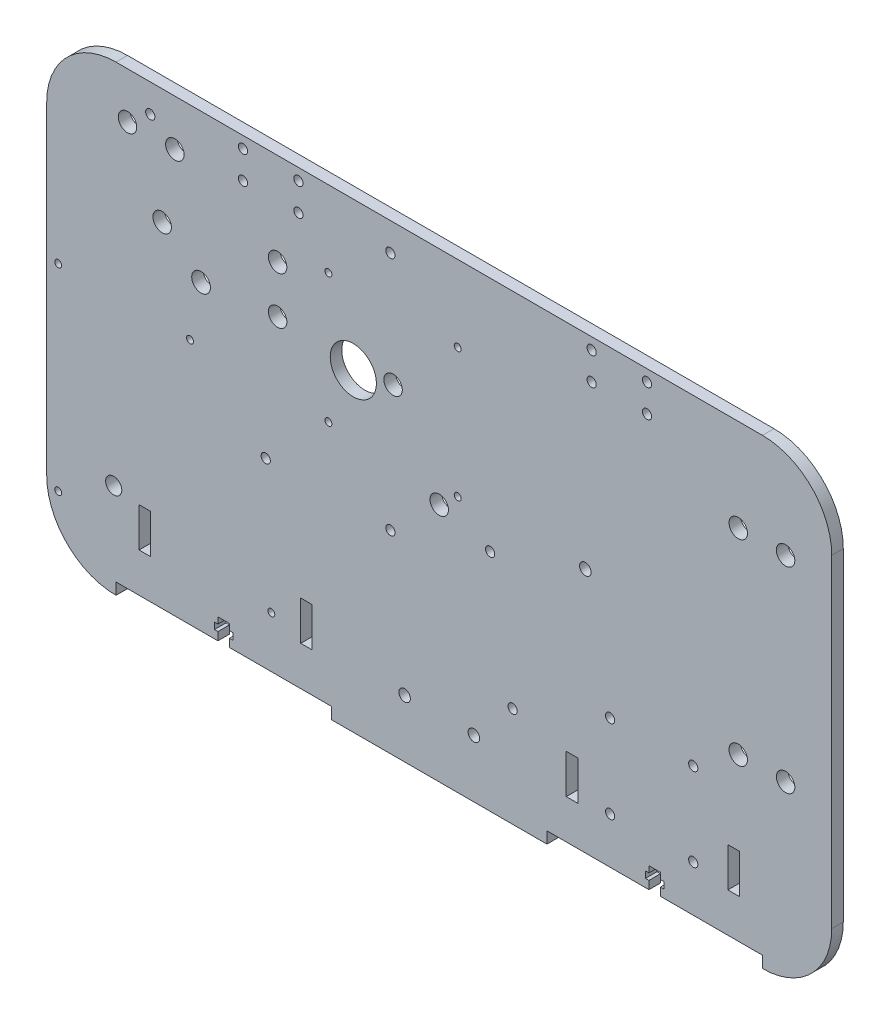
SolidWorks part; units mm, degrees
ref_plane "Alzado" through (0, 0, 0) normal (0, 0, 1) x (1, 0, 0)
ref_plane "Planta" through (0, 0, 0) normal (0, 1, 0) x (1, 0, 0)
ref_plane "Vista lateral" through (0, 0, 0) normal (1, 0, 0) x (0, 0, -1)
sketch "Croquis1" plane through (0, 0, 0) normal (0, 0, 1) x (1, 0, 0)
  line L1 (30, 0) -> (310, 0)
  line L2 (0, 30) -> (0, 170)
  line L3 (30, 200) -> (310, 200)
  line L4 (340, 30) -> (340, 170)
  arc A0 (30, 0) -> (0, 30) centre (30, 30) cw
  arc A1 (310, 0) -> (340, 30) centre (310, 30) ccw
  arc A2 (310, 200) -> (340, 170) centre (310, 170) cw
  arc A3 (0, 170) -> (30, 200) centre (30, 170) cw
  point P7 (0, 0)
  point P12 (340, 200)
  point P15 (0, 200)
  dimension "D3" = 30
  dimension "D1" = 200
  dimension "D2" = 340
extrude "Saliente-Extruir1" add sketch "Croquis1" along normal blind 5
sketch "Croquis2" plane through (0, 0, 5) normal (0, 0, -1) x (-1, 0, 0)
  line L0 (-55.5, 180) -> (-35, 180) construction
  line L2 (-310, 200) -> (-30, 200) construction
  line L3 (0, 170) -> (0, 30) construction
  line L4 (-100, 160) -> (-100, 139.5) construction
  line L5 (-310, 200) -> (-30, 200) construction
  line L6 (-299.5, 160) -> (-320, 160) construction
  line L7 (-340, 30) -> (-340, 170) construction
  line L8 (-320, 75) -> (-299.5, 75) construction
  line L9 (-30, 0) -> (-310, 0) construction
  line L10 (-100, 149.75) -> (-146.5265, 149.75) construction
  circle A0 centre (-55.5, 180) radius 4
  circle A1 centre (-35, 180) radius 4
  circle A2 centre (-100, 160) radius 4
  circle A3 centre (-100, 139.5) radius 4
  circle A4 centre (-299.5, 160) radius 4
  circle A5 centre (-320, 160) radius 4
  circle A6 centre (-320, 75) radius 4
  circle A7 centre (-299.5, 75) radius 4
  circle A8 centre (-150, 139) radius 4
  circle A9 centre (-170, 104) radius 4
  circle A10 centre (-50, 150) radius 4
  dimension "D1" = 8
  dimension "D10" = 40
  dimension "D14" = 8
  dimension "D19" = 8
  dimension "D2" = 20.5
  dimension "D3" = 35
  dimension "D4" = 20
  dimension "D5" = 20.5
  dimension "D6" = 40
  dimension "D7" = 100
  dimension "D8" = 20.5
  dimension "D9" = 20
  dimension "D11" = 20.5
  dimension "D12" = 20
  dimension "D13" = 75
  dimension "D15" = 150
  dimension "D16" = 61
  dimension "D17" = 35
  dimension "D18" = 20
  dimension "D20" = 50
  dimension "D21" = 50
extrude "Cortar-Extruir4" cut sketch "Croquis2" along normal blind 10
sketch "Croquis3" plane through (0, 0, 0) normal (0, 0, -1) x (-1, 0, 0)
  line L0 (-44.85, 187.84) -> (-148.85, 187.84) construction
  line L1 (-148.85, 187.84) -> (-148.85, 83.84) construction
  line L2 (-148.85, 83.84) -> (-94.85, 83.84) construction
  line L3 (-94.85, 83.84) -> (-44.85, 187.84) construction
  line L4 (-310, 200) -> (-30, 200) construction
  line L5 (0, 170) -> (0, 30) construction
  circle A0 centre (-148.85, 83.84) radius 2
  circle A1 centre (-94.85, 83.84) radius 2
  circle A2 centre (-44.85, 187.84) radius 2
  circle A3 centre (-148.85, 187.84) radius 2
  circle A4 centre (-132.79, 135.84) radius 10
  circle A5 centre (-66.85, 135.84) radius 4.05
  dimension "D1" = 4
  dimension "D5" = 20
  dimension "D6" = 8.1
  dimension "D2" = 104
  dimension "D3" = 104
  dimension "D4" = 54
  dimension "D7" = 16.06
  dimension "D8" = 52
  dimension "D9" = 52
  dimension "D10" = 82
  dimension "D11" = 12.16
  dimension "D12" = 66.85
extrude "Cortar-Extruir5" cut sketch "Croquis3" against normal blind 10
sketch "Croquis5" plane through (0, 0, 0) normal (0, 0, -1) x (-1, 0, 0)
  line L0 (-178, 167) -> (-122, 167) construction
  line L1 (-122, 167) -> (-122, 111) construction
  line L2 (-178, 167) -> (-178, 111) construction
  line L3 (-178, 111) -> (-122, 111) construction
  line L4 (-310, 200) -> (-30, 200) construction
  line L7 (0, 170) -> (0, 30) construction
  circle A0 centre (-178, 167) radius 1.5
  circle A1 centre (-122, 111) radius 1.5
  circle A2 centre (-122, 167) radius 1.5
  circle A3 centre (-178, 111) radius 1.5
  dimension "D1" = 3
  dimension "D4" = 3
  dimension "D2" = 56
  dimension "D3" = 56
  dimension "D5" = 33
  dimension "D6" = 122
extrude "Cortar-Extruir6" cut sketch "Croquis5" against normal blind 10
sketch "Croquis6" plane through (0, 0, 5) normal (0, 0, 1) x (1, 0, 0)
  line L0 (244, 61) -> (280, 61) construction
  line L1 (244, 61) -> (244, 25) construction
  line L2 (244, 25) -> (280, 25) construction
  line L3 (280, 25) -> (280, 61) construction
  line L4 (340, 30) -> (340, 170) construction
  line L5 (30, 0) -> (310, 0) construction
  circle A0 centre (244, 61) radius 2
  circle A1 centre (280, 61) radius 2
  circle A2 centre (244, 25) radius 2
  circle A3 centre (280, 25) radius 2
  dimension "D1" = 4
  dimension "D2" = 36
  dimension "D3" = 36
  dimension "D4" = 60
  dimension "D5" = 25
extrude "Cortar-Extruir7" cut sketch "Croquis6" against normal blind 10
sketch "Croquis7" plane through (0, 0, 5) normal (0, 0, 1) x (1, 0, 0)
  line L4 (30, 0) -> (310, 0)
  line L5 (340, 30) -> (340, 170)
  line L6 (310, 200) -> (30, 200)
  line L7 (0, 170) -> (0, 30)
  line L8 (30, 0) -> (310, 0)
  line L9 (340, 30) -> (340, 170)
  line L10 (310, 200) -> (30, 200)
  line L11 (0, 170) -> (0, 30)
  circle A0 centre (50, 150) radius 4 construction
  circle A1 centre (100, 160) radius 4 construction
  circle A2 centre (100, 139.5) radius 4 construction
  circle A3 centre (299.5, 75) radius 4 construction
  arc A4 (0, 30) -> (30, 0) centre (30, 30) ccw
  arc A5 (310, 0) -> (340, 30) centre (310, 30) ccw
  arc A6 (340, 170) -> (310, 200) centre (310, 170) ccw
  arc A7 (30, 200) -> (0, 170) centre (30, 170) ccw
  arc A8 (0, 30) -> (30, 0) centre (30, 30) ccw
  arc A9 (310, 0) -> (340, 30) centre (310, 30) ccw
  arc A10 (340, 170) -> (310, 200) centre (310, 170) ccw
  arc A11 (30, 200) -> (0, 170) centre (30, 170) ccw
  circle A12 centre (320, 75) radius 4 construction
  circle A13 centre (299.5, 160) radius 4 construction
  circle A14 centre (320, 160) radius 4 construction
  circle A15 centre (55.5, 180) radius 4 construction
  circle A16 centre (35, 180) radius 4 construction
  circle A17 centre (50, 150) radius 4
  circle A18 centre (100, 160) radius 4
  circle A19 centre (100, 139.5) radius 4
  circle A20 centre (299.5, 75) radius 4
  circle A21 centre (320, 75) radius 4
  circle A22 centre (299.5, 160) radius 4
  circle A23 centre (320, 160) radius 4
  circle A24 centre (55.5, 180) radius 4
  circle A25 centre (35, 180) radius 4
  dimension "D1" = 0
sketch "Croquis8" plane through (0, 0, 5) normal (0, 0, 1) x (1, 0, 0)
  line L0 (236, 195) -> (236, 183) construction
  line L1 (236, 195) -> (260, 195) construction
  line L2 (236, 183) -> (260, 183) construction
  line L3 (260, 183) -> (260, 195) construction
  line L4 (85, 195) -> (85, 183) construction
  line L5 (85, 195) -> (109, 195) construction
  line L6 (85, 183) -> (109, 183) construction
  line L7 (109, 183) -> (109, 195) construction
  line L8 (310, 200) -> (30, 200) construction
  line L9 (340, 30) -> (340, 170) construction
  line L10 (0, 170) -> (0, 30) construction
  circle A0 centre (236, 195) radius 2
  circle A1 centre (236, 183) radius 2
  circle A2 centre (260, 183) radius 2
  circle A3 centre (260, 195) radius 2
  circle A4 centre (85, 195) radius 2
  circle A5 centre (85, 183) radius 2
  circle A6 centre (109, 183) radius 2
  circle A7 centre (109, 195) radius 2
  dimension "D1" = 24
  dimension "D2" = 12
  dimension "D3" = 24
  dimension "D4" = 12
  dimension "D5" = 5
  dimension "D6" = 80
  dimension "D7" = 85
extrude "Cortar-Extruir8" cut sketch "Croquis8" against normal blind 10
sketch "Croquis9" plane through (0, 0, 0) normal (0, 0, -1) x (-1, 0, 0)
  line L0 (-233.2967, 111.4949) -> (-201.8, 43.4) construction
  line L1 (-201.8, 43.4) -> (-192.05, 97.4132) construction
  line L2 (-192.05, 97.4132) -> (-233.2967, 111.4949) construction
  line L3 (-62.0804, 111.91) -> (-4.98, 111.91) construction
  line L4 (-4.98, 111.91) -> (-4.98, 26.56) construction
  line L5 (-4.98, 26.56) -> (-97.2809, 27.16) construction
  line L6 (-62.0804, 111.91) -> (-97.2809, 27.16) construction
  line L8 (-30, 0) -> (-310, 0) construction
  line L9 (0, 170) -> (0, 30) construction
  line L10 (-340, 30) -> (-340, 170) construction
  circle A0 centre (-29.01, 40.6565) radius 3.5
  circle A1 centre (-62.0804, 111.91) radius 1.5
  circle A2 centre (-4.98, 111.91) radius 1.5
  circle A3 centre (-97.2809, 27.16) radius 1.5
  circle A4 centre (-4.98, 26.56) radius 1.5
  circle A5 centre (-233.2967, 111.4949) radius 2.5
  circle A6 centre (-201.8, 43.4) radius 2
  circle A7 centre (-192.05, 97.4132) radius 2
  dimension "D1" = 24.03
  dimension "D2" = 13.94
  dimension "D3" = 26.56
  dimension "D4" = 4.98
  dimension "D5" = 54.8862
  dimension "D6" = 43.5843
  dimension "D7" = 75.0264
  dimension "D8" = 43.4
  dimension "D9" = 138.2
extrude "Cortar-Extruir9" cut sketch "Croquis9" against normal blind 10
sketch "Croquis10" plane through (0, 0, 5) normal (0, 0, 1) x (1, 0, 0)
  line L0 (123.3333, 5) -> (123.3333, 0)
  line L1 (30, 0) -> (310, 0)
  line L2 (30, 0) -> (30, 5)
  line L3 (30, 5) -> (310, 5)
  line L4 (310, 0) -> (310, 5)
  line L5 (216.6667, 5) -> (216.6667, 0)
  point P10 (30, 2.5)
  line M48 (30, 0) -> (310, 0)
  dimension "D1" = 93.3333
  dimension "D2" = 93.3333
  dimension "D3" = 5
extrude "Cortar-Extruir10" cut sketch "Croquis10" against normal blind 10 contours L3 L2 L0 M48 | L3 L5 L1 L4 region at (76.6667, 2.5, 5) region at (263.3333, 2.5, 5)
sketch "Croquis12" plane through (0, 0, 5) normal (0, 0, 1) x (1, 0, 0)
  line L0 (76.6667, 5) -> (76.6667, 14) construction
  line L1 (30, 5) -> (123.3333, 5) construction
  line L2 (170, 0) -> (170, 18.6393) construction
  line L3 (123.3333, 0) -> (216.6667, 0) construction
  line L4 (74.1667, 5) -> (74.1667, 8.5)
  line L5 (74.1667, 8.5) -> (72.6667, 8.5)
  line L6 (72.6667, 8.5) -> (72.6667, 11.3)
  line L7 (72.6667, 11.3) -> (74.1667, 11.3)
  line L8 (74.1667, 11.3) -> (74.1667, 14)
  line L9 (74.1667, 14) -> (79.1667, 14)
  line L10 (79.1667, 8.5) -> (80.6667, 8.5)
  line L11 (79.1667, 5) -> (79.1667, 8.5)
  line L12 (80.6667, 8.5) -> (80.6667, 11.3)
  line L13 (80.6667, 11.3) -> (79.1667, 11.3)
  line L14 (79.1667, 11.3) -> (79.1667, 14)
  line L15 (263.3333, 5) -> (263.3333, 14) construction
  line L16 (260.8333, 11.3) -> (260.8333, 14)
  line L17 (259.3333, 11.3) -> (260.8333, 11.3)
  line L18 (259.3333, 8.5) -> (259.3333, 11.3)
  line L19 (260.8333, 5) -> (260.8333, 8.5)
  line L20 (260.8333, 8.5) -> (259.3333, 8.5)
  line L21 (265.8333, 14) -> (260.8333, 14)
  line L22 (265.8333, 11.3) -> (265.8333, 14)
  line L23 (267.3333, 11.3) -> (265.8333, 11.3)
  line L24 (267.3333, 8.5) -> (267.3333, 11.3)
  line L25 (265.8333, 8.5) -> (267.3333, 8.5)
  line L26 (265.8333, 5) -> (265.8333, 8.5)
  line L27 (74.1667, 5) -> (79.1667, 5)
  line L28 (260.8333, 5) -> (265.8333, 5)
  point P1 (76.6667, 14)
  dimension "D1" = 2.8
  dimension "D2" = 4
  dimension "D3" = 9
  dimension "D4" = 3.5
  dimension "D5" = 2.5
extrude "Cortar-Extruir14" cut sketch "Croquis12" against normal blind 5
sketch "Croquis13" plane through (0, 0, 5) normal (0, 0, 1) x (1, 0, 0)
  line L0 (170, 0) -> (170, 28.0268) construction
  line L1 (123.3333, 0) -> (216.6667, 0) construction
  line L2 (79.1667, 5) -> (123.3333, 5) construction
  line L3 (110, 5) -> (115, 5)
  line L4 (110, 5) -> (110, 39)
  line L5 (110, 39) -> (115, 39)
  line L6 (115, 5) -> (115, 39)
  line L7 (225, 5) -> (225, 39)
  line L8 (230, 39) -> (225, 39)
  line L9 (230, 5) -> (230, 39)
  line L10 (230, 5) -> (225, 5)
  line L11 (110, 22) -> (115, 22)
  line L12 (225, 22) -> (230, 22)
  line L13 (30, 5) -> (74.1667, 5) construction
  line L14 (40, 5) -> (45, 5)
  line L15 (40, 5) -> (40, 39)
  line L16 (40, 39) -> (45, 39)
  line L17 (45, 5) -> (45, 39)
  line L18 (40, 22) -> (45, 22)
  line L19 (300, 22) -> (295, 22)
  line L20 (295, 5) -> (295, 39)
  line L21 (300, 39) -> (295, 39)
  line L22 (300, 5) -> (300, 39)
  line L23 (300, 5) -> (295, 5)
  dimension "D1" = 5
  dimension "D2" = 60
  dimension "D3" = 34
  dimension "D4" = 5
  dimension "D5" = 70
extrude "Cortar-Extruir15" cut sketch "Croquis13" against normal blind 5 contours L15 L18 L17 L16 | L4 L11 L6 L5 | L7 L12 L9 L8 | L19 L22 L21 L20 region at (112.5, 30.5, 5) region at (227.5, 30.5, 5) region at (42.5, 30.5, 5) region at (297.5, 30.5, 5)
sketch "Croquis14" plane through (0, 0, 5) normal (0, 0, 1) x (1, 0, 0)
  line L0 (170, 0) -> (170, 25) construction
  line L1 (123.3333, 0) -> (216.6667, 0) construction
  line L2 (155, 25) -> (170, 25) construction
  line L3 (79.1667, 5) -> (123.3333, 5) construction
  circle A0 centre (155, 25) radius 2.5
  circle A1 centre (185, 25) radius 2.5
  dimension "D2" = 5
  dimension "D1" = 15
  dimension "D3" = 20
extrude "Cortar-Extruir16" cut sketch "Croquis14" against normal blind 10
sketch "Croquis15" plane through (0, 0, 5) normal (0, 0, 1) x (1, 0, 0)
  line L0 (300, 39) -> (295, 39) construction
  line L1 (300, 22) -> (300, 39) construction
  line L2 (295, 22) -> (295, 39) construction
  line L3 (300, 22) -> (295, 22) construction
  line L4 (225, 22) -> (230, 22) construction
  line L5 (230, 39) -> (225, 39) construction
  line L6 (230, 22) -> (230, 39) construction
  line L7 (225, 22) -> (225, 39) construction
  line L8 (110, 39) -> (115, 39) construction
  line L9 (115, 22) -> (115, 39) construction
  line L10 (110, 22) -> (110, 39) construction
  line L11 (110, 22) -> (115, 22) construction
  line L12 (40, 22) -> (45, 22) construction
  line L13 (40, 39) -> (45, 39) construction
  line L14 (45, 22) -> (45, 39) construction
  line L15 (40, 22) -> (40, 39) construction
  line L16 (300, 39) -> (295, 39)
  line L17 (300, 22) -> (300, 39)
  line L18 (295, 22) -> (295, 39)
  line L19 (300, 22) -> (295, 22)
  line L20 (225, 22) -> (230, 22)
  line L21 (230, 39) -> (225, 39)
  line L22 (230, 22) -> (230, 39)
  line L23 (225, 22) -> (225, 39)
  line L24 (110, 39) -> (115, 39)
  line L25 (115, 22) -> (115, 39)
  line L26 (110, 22) -> (110, 39)
  line L27 (110, 22) -> (115, 22)
  line L28 (40, 22) -> (45, 22)
  line L29 (40, 39) -> (45, 39)
  line L30 (45, 22) -> (45, 39)
  line L31 (40, 22) -> (40, 39)
  line L34 (267.3333, 8.5) -> (265.8333, 8.5)
  line L35 (265.8333, 8.5) -> (265.8333, 5)
  line L36 (265.8333, 5) -> (310, 5)
  line L37 (310, 5) -> (310, 0)
  line L38 (340, 30) -> (340, 170)
  line L39 (310, 200) -> (30, 200)
  line L40 (0, 170) -> (0, 30)
  line L41 (30, 0) -> (30, 5)
  line L42 (30, 5) -> (74.1667, 5)
  line L43 (74.1667, 5) -> (74.1667, 8.5)
  line L44 (74.1667, 8.5) -> (72.6667, 8.5)
  line L45 (72.6667, 8.5) -> (72.6667, 11.3)
  line L46 (72.6667, 11.3) -> (74.1667, 11.3)
  line L47 (74.1667, 11.3) -> (74.1667, 14)
  line L48 (74.1667, 14) -> (79.1667, 14)
  line L49 (79.1667, 14) -> (79.1667, 11.3)
  line L50 (79.1667, 11.3) -> (80.6667, 11.3)
  line L51 (80.6667, 11.3) -> (80.6667, 8.5)
  line L52 (80.6667, 8.5) -> (79.1667, 8.5)
  line L53 (79.1667, 8.5) -> (79.1667, 5)
  line L54 (79.1667, 5) -> (123.3333, 5)
  line L55 (123.3333, 5) -> (123.3333, 0)
  line L56 (123.3333, 0) -> (216.6667, 0)
  line L57 (216.6667, 0) -> (216.6667, 5)
  line L58 (216.6667, 5) -> (260.8333, 5)
  line L59 (260.8333, 5) -> (260.8333, 8.5)
  line L60 (260.8333, 8.5) -> (259.3333, 8.5)
  line L61 (259.3333, 8.5) -> (259.3333, 11.3)
  line L62 (259.3333, 11.3) -> (260.8333, 11.3)
  line L63 (260.8333, 11.3) -> (260.8333, 14)
  line L64 (260.8333, 14) -> (265.8333, 14)
  line L65 (265.8333, 14) -> (265.8333, 11.3)
  line L66 (265.8333, 11.3) -> (267.3333, 11.3)
  line L67 (267.3333, 11.3) -> (267.3333, 8.5)
  line L68 (267.3333, 8.5) -> (265.8333, 8.5)
  line L69 (265.8333, 8.5) -> (265.8333, 5)
  line L70 (265.8333, 5) -> (310, 5)
  line L71 (310, 5) -> (310, 0)
  line L72 (340, 30) -> (340, 170)
  line L73 (310, 200) -> (30, 200)
  line L74 (0, 170) -> (0, 30)
  line L75 (30, 0) -> (30, 5)
  line L76 (30, 5) -> (74.1667, 5)
  line L77 (74.1667, 5) -> (74.1667, 8.5)
  line L78 (74.1667, 8.5) -> (72.6667, 8.5)
  line L79 (72.6667, 8.5) -> (72.6667, 11.3)
  line L80 (72.6667, 11.3) -> (74.1667, 11.3)
  line L81 (74.1667, 11.3) -> (74.1667, 14)
  line L82 (74.1667, 14) -> (79.1667, 14)
  line L83 (79.1667, 14) -> (79.1667, 11.3)
  line L84 (79.1667, 11.3) -> (80.6667, 11.3)
  line L85 (80.6667, 11.3) -> (80.6667, 8.5)
  line L86 (80.6667, 8.5) -> (79.1667, 8.5)
  line L87 (79.1667, 8.5) -> (79.1667, 5)
  line L88 (79.1667, 5) -> (123.3333, 5)
  line L89 (123.3333, 5) -> (123.3333, 0)
  line L90 (123.3333, 0) -> (216.6667, 0)
  line L91 (216.6667, 0) -> (216.6667, 5)
  line L92 (216.6667, 5) -> (260.8333, 5)
  line L93 (260.8333, 5) -> (260.8333, 8.5)
  line L94 (260.8333, 8.5) -> (259.3333, 8.5)
  line L95 (259.3333, 8.5) -> (259.3333, 11.3)
  line L96 (259.3333, 11.3) -> (260.8333, 11.3)
  line L97 (260.8333, 11.3) -> (260.8333, 14)
  line L98 (260.8333, 14) -> (265.8333, 14)
  line L99 (265.8333, 14) -> (265.8333, 11.3)
  line L100 (265.8333, 11.3) -> (267.3333, 11.3)
  line L101 (267.3333, 11.3) -> (267.3333, 8.5)
  circle A0 centre (201.8, 43.4) radius 2 construction
  circle A1 centre (185, 25) radius 2.5 construction
  circle A2 centre (155, 25) radius 2.5 construction
  circle A3 centre (244, 25) radius 2 construction
  arc A4 (310, 0) -> (340, 30) centre (310, 30) ccw
  arc A5 (340, 170) -> (310, 200) centre (310, 170) ccw
  arc A6 (30, 200) -> (0, 170) centre (30, 170) ccw
  arc A7 (0, 30) -> (30, 0) centre (30, 30) ccw
  arc A8 (310, 0) -> (340, 30) centre (310, 30) ccw
  arc A9 (340, 170) -> (310, 200) centre (310, 170) ccw
  arc A10 (30, 200) -> (0, 170) centre (30, 170) ccw
  arc A11 (0, 30) -> (30, 0) centre (30, 30) ccw
  circle A12 centre (280, 25) radius 2 construction
  circle A13 centre (280, 61) radius 2 construction
  circle A14 centre (299.5, 160) radius 4 construction
  circle A15 centre (320, 160) radius 4 construction
  circle A16 centre (320, 75) radius 4 construction
  circle A17 centre (299.5, 75) radius 4 construction
  circle A18 centre (244, 61) radius 2 construction
  circle A19 centre (192.05, 97.4132) radius 2 construction
  circle A20 centre (233.2967, 111.4949) radius 2.5 construction
  circle A21 centre (260, 183) radius 2 construction
  circle A22 centre (260, 195) radius 2 construction
  circle A23 centre (236, 195) radius 2 construction
  circle A24 centre (236, 183) radius 2 construction
  circle A25 centre (178, 167) radius 1.5 construction
  circle A26 centre (178, 111) radius 1.5 construction
  circle A27 centre (170, 104) radius 4 construction
  circle A28 centre (148.85, 83.84) radius 2 construction
  circle A29 centre (150, 139) radius 4 construction
  circle A30 centre (148.85, 187.84) radius 2 construction
  circle A31 centre (122, 167) radius 1.5 construction
  circle A32 centre (132.79, 135.84) radius 10 construction
  circle A33 centre (122, 111) radius 1.5 construction
  circle A34 centre (94.85, 83.84) radius 2 construction
  circle A35 centre (97.2809, 27.16) radius 1.5 construction
  circle A36 centre (4.98, 26.56) radius 1.5 construction
  circle A37 centre (29.01, 40.6565) radius 3.5 construction
  circle A38 centre (4.98, 111.91) radius 1.5 construction
  circle A39 centre (62.0804, 111.91) radius 1.5 construction
  circle A40 centre (66.85, 135.84) radius 4.05 construction
  circle A41 centre (100, 139.5) radius 4 construction
  circle A42 centre (100, 160) radius 4 construction
  circle A43 centre (109, 183) radius 2 construction
  circle A44 centre (109, 195) radius 2 construction
  circle A45 centre (85, 195) radius 2 construction
  circle A46 centre (85, 183) radius 2 construction
  circle A47 centre (50, 150) radius 4 construction
  circle A48 centre (44.85, 187.84) radius 2 construction
  circle A49 centre (55.5, 180) radius 4 construction
  circle A50 centre (35, 180) radius 4 construction
  circle A51 centre (201.8, 43.4) radius 2
  circle A52 centre (185, 25) radius 2.5
  circle A53 centre (155, 25) radius 2.5
  circle A54 centre (244, 25) radius 2
  circle A55 centre (280, 25) radius 2
  circle A56 centre (280, 61) radius 2
  circle A57 centre (299.5, 160) radius 4
  circle A58 centre (320, 160) radius 4
  circle A59 centre (320, 75) radius 4
  circle A60 centre (299.5, 75) radius 4
  circle A61 centre (244, 61) radius 2
  circle A62 centre (192.05, 97.4132) radius 2
  circle A63 centre (233.2967, 111.4949) radius 2.5
  circle A64 centre (260, 183) radius 2
  circle A65 centre (260, 195) radius 2
  circle A66 centre (236, 195) radius 2
  circle A67 centre (236, 183) radius 2
  circle A68 centre (178, 167) radius 1.5
  circle A69 centre (178, 111) radius 1.5
  circle A70 centre (170, 104) radius 4
  circle A71 centre (148.85, 83.84) radius 2
  circle A72 centre (150, 139) radius 4
  circle A73 centre (148.85, 187.84) radius 2
  circle A74 centre (122, 167) radius 1.5
  circle A75 centre (132.79, 135.84) radius 10
  circle A76 centre (122, 111) radius 1.5
  circle A77 centre (94.85, 83.84) radius 2
  circle A78 centre (97.2809, 27.16) radius 1.5
  circle A79 centre (4.98, 26.56) radius 1.5
  circle A80 centre (29.01, 40.6565) radius 3.5
  circle A81 centre (4.98, 111.91) radius 1.5
  circle A82 centre (62.0804, 111.91) radius 1.5
  circle A83 centre (66.85, 135.84) radius 4.05
  circle A84 centre (100, 139.5) radius 4
  circle A85 centre (100, 160) radius 4
  circle A86 centre (109, 183) radius 2
  circle A87 centre (109, 195) radius 2
  circle A88 centre (85, 195) radius 2
  circle A89 centre (85, 183) radius 2
  circle A90 centre (50, 150) radius 4
  circle A91 centre (44.85, 187.84) radius 2
  circle A92 centre (55.5, 180) radius 4
  circle A93 centre (35, 180) radius 4
  dimension "D1" = 0
